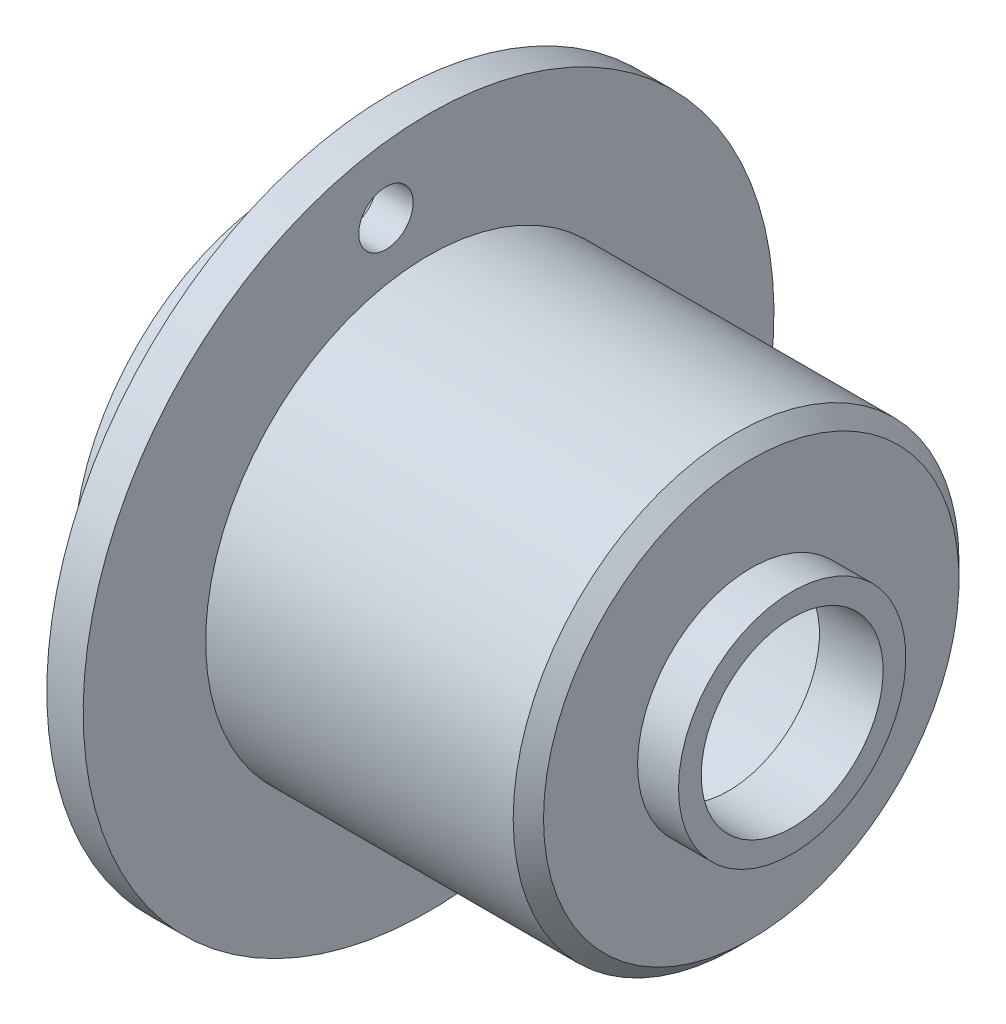
SolidWorks part; units mm, degrees
material "6061-T6 (SS)"
ref_plane "Front Plane" through (0, 0, 0) normal (0, 0, 1) x (1, 0, 0)
ref_plane "Top Plane" through (0, 0, 0) normal (0, 1, 0) x (1, 0, 0)
ref_plane "Right Plane" through (0, 0, 0) normal (1, 0, 0) x (0, 0, -1)
other "Center of Mass"
ref_plane "Plane3" through (-27.4281, 0, 0) normal (1, 0, 0) x (0, 0, -1)
sketch "Sketch1" plane through (-27.4281, 0, 0) normal (1, 0, 0) x (0, 0, -1)
  line L0 (0, 0) -> (-2.9763, 19.3027) construction
  line L1 (-0.1069, 15.7295) -> (1.5529, 20.0011) construction
  line L2 (1.5529, 20.0011) -> (-1.3165, 23.5743) construction
  line L3 (-1.3165, 23.5743) -> (-5.8456, 22.876) construction
  line L4 (-5.8456, 22.876) -> (-7.5055, 18.6044) construction
  line L5 (-7.5055, 18.6044) -> (-4.6361, 15.0312) construction
  line L6 (-4.6361, 15.0312) -> (-0.1069, 15.7295) construction
  line L7 (4.6361, -15.0312) -> (0.1069, -15.7295) construction
  line L8 (0.1069, -15.7295) -> (-1.5529, -20.0011) construction
  line L9 (-1.5529, -20.0011) -> (1.3165, -23.5743) construction
  line L10 (1.3165, -23.5743) -> (5.8456, -22.876) construction
  line L11 (5.8456, -22.876) -> (7.5055, -18.6044) construction
  line L12 (7.5055, -18.6044) -> (4.6361, -15.0312) construction
  line L13 (-7.5055, 18.6044) -> (1.5529, 20.0011) construction
  line L15 (0, 0) -> (11.8051, 1.8202) construction
  circle A0 centre (0, 0) radius 13.9746
  circle A1 centre (0, 0) radius 15.5621 construction
  circle A3 centre (2.9763, -19.3027) radius 3.9688 construction
  arc A8 (-10.0197, 11.9073) -> (-5.9677, -14.3724) centre (0, 0) ccw
  arc A9 (5.9677, 14.3724) -> (10.0197, -11.9073) centre (0, 0) cw
  circle A16 centre (-2.9763, 19.3027) radius 2.667 construction
  circle A17 centre (2.9763, -19.3027) radius 2.667 construction
  circle A19 centre (-2.9763, 19.3027) radius 2.1526 construction
  arc A20 (-10.0197, 11.9073) -> (-7.5055, 18.6044) centre (-14.7192, 17.4921) ccw
  arc A21 (-7.5055, 18.6044) -> (1.5529, 20.0011) centre (-2.9763, 19.3027) cw
  arc A22 (1.5529, 20.0011) -> (5.9677, 14.3724) centre (8.7667, 21.1134) ccw
  arc A23 (7.5055, -18.6044) -> (10.0197, -11.9073) centre (14.7192, -17.4921) cw
  arc A24 (-1.5529, -20.0011) -> (7.5055, -18.6044) centre (2.9763, -19.3027) ccw
  arc A25 (-5.9677, -14.3724) -> (-1.5529, -20.0011) centre (-8.7667, -21.1134) cw
  circle A27 centre (-2.9763, 19.3027) radius 2.1526 construction
  point P4 (-2.3715, 15.3803)
  dimension "D1" = 27.9492
  dimension "D4" = 5.334
  dimension "D2" = 1.5875
  dimension "D3" = 7.9375
extrude "Boss-Extrude1" add sketch "Sketch1" along normal blind 2.54
sketch "Sketch2" plane through (-24.8881, 0, 0) normal (1, 0, 0) x (0, 0, -1)
  circle A0 centre (0, 0) radius 13.9746
  circle A1 centre (0, 0) radius 15.5621
  arc A2 (-10.0197, 11.9073) -> (-5.9677, -14.3724) centre (0, 0) ccw construction
  circle A3 centre (0, 0) radius 13.9746 construction
extrude "Boss-Extrude2" add sketch "Sketch2" along normal offset from surface (20.94 mm away) 23.48 up to face at (-27.4281, 0, 0)
sketch "Sketch5" plane through (0, 0, 0) normal (0, 0, 1) x (1, 0, 0)
  line L1 (0.4969, 7.9375) -> (0.4969, 6.35)
  line L3 (-3.9481, -15.5621) -> (-3.9481, 15.5621) construction
  line L4 (-3.9481, 6.35) -> (-3.9481, 15.5621)
  line L5 (0, 0) -> (45.5597, 0) construction
  line L6 (-3.9481, 6.35) -> (0.4969, 6.35)
  line L9 (0.4969, 7.9375) -> (-2.3606, 7.9375)
  line L10 (-2.3606, 7.9375) -> (-2.3606, 14.5038)
  line L12 (-2.3606, 14.5038) -> (-3.419, 15.5621)
  line L13 (-3.419, 15.5621) -> (-3.9481, 15.5621)
  line L14 (-3.9481, 13.9746) -> (-2.8898, 15.0329) construction
  dimension "D2" = 4.445
  dimension "D1" = 12.7
  dimension "D3" = 1.5875
  dimension "D4" = 1.5875
revolve "Revolve1" add sketch "Sketch5" angle 360 about L5
sketch "Sketch3" plane through (-27.4281, 0, 0) normal (-1, 0, 0) x (0, 0, 1)
  circle A0 centre (0, 0) radius 13.9746
  circle A1 centre (0, 0) radius 15.2446
  circle A2 centre (0, 0) radius 13.9746 construction
  dimension "D1" = 1.27
extrude "Boss-Extrude3" add sketch "Sketch3" along normal blind 7
sketch "Sketch6" [suppressed] plane through (0, 0, 0) normal (0, 0, 1) x (1, 0, 0)
  line L0 (-25.4, -23.8855) -> (-25.2167, -23.8855)
  line L1 (-18.1358, -23.8855) -> (-15.5958, -23.8855) construction
  line L2 (-25.4, -23.8855) -> (-25.4, -25.4)
  line L3 (-18.1358, -18.6044) -> (-18.1358, -23.8855) construction
  arc A0 (-25.4, -25.4) -> (-25.087, -27.369) centre (-19.05, -25.4) ccw construction
  arc A1 (-25.2167, -23.8855) -> (-25.4, -25.4) centre (-19.05, -25.4) cw
extrude "Copying Eruption" [suppressed] cut sketch "Sketch6" against normal through all both and the other way through all
hole_wizard "#6 Clearance Hole1" positions "Sketch7" profile "Sketch8" hole size "#6" standard "ANSI Inch" end condition up to next
sketch "Sketch7" plane through (-24.8881, 0, 0) normal (1, 0, 0) x (0, 0, -1)
  point P0 (-2.9763, 19.3027)
  point P3 (2.9763, -19.3027)
sketch "Sketch8" plane through (-24.8881, 19.3027, 2.9763) normal (0, 1, 0) x (0, 0, -1)
  line L0 (0, 0) -> (0, 2.54)
  line L1 (0, 2.54) -> (1.8986, 2.54)
  line L2 (1.8986, 2.54) -> (1.8986, 0)
  line L5 (1.8986, 0) -> (0, 0)
  line L11 (0, -6.35) -> (0, 107.95) construction
  dimension "Thru Hole Dia." = 3.7973
  dimension "Thru Hole Depth" = 2.54
sketch "Sketch9" plane through (-24.8881, 0, 0) normal (1, 0, 0) x (0, 0, -1)
  circle A0 centre (0, 0) radius 15.5621 construction
  circle A1 centre (0, 0) radius 15.5621
  circle A2 centre (0, 0) radius 24.1136
  arc A3 (1.5529, 20.0011) -> (-7.5055, 18.6044) centre (-2.9763, 19.3027) ccw construction
  circle A4 centre (2.9763, -19.3027) radius 1.8986 construction
  circle A5 centre (-2.9763, 19.3027) radius 1.8986 construction
  circle A6 centre (2.9763, -19.3027) radius 1.8986
  circle A7 centre (-2.9763, 19.3027) radius 1.8986
extrude "Boss-Extrude4" add sketch "Sketch9" against normal up to surface (2.54 mm away) up to face at (-27.4281, 17.4041, 2.9763)
equation "\"motor diameter\"= 28mm"
equation "\"D1@Sketch1\"=\"motor diameter\"-0.002in"
equation "\"D1@Boss-Extrude3\"=7mm"
equation "\"D2@Sketch5\"=0.175"
